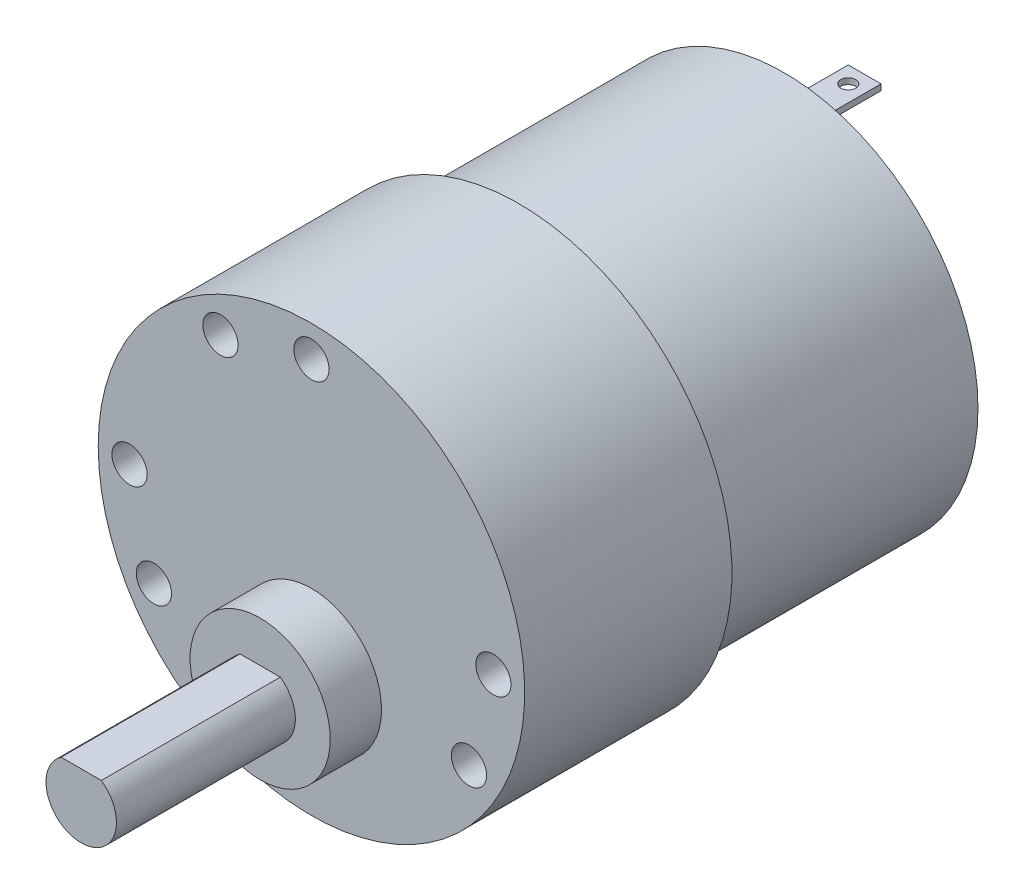
SolidWorks part; units mm, degrees
ref_plane "Front Plane" through (0, 0, 0) normal (0, 0, 1) x (1, 0, 0)
ref_plane "Top Plane" through (0, 0, 0) normal (0, 1, 0) x (1, 0, 0)
ref_plane "Right Plane" through (0, 0, 0) normal (1, 0, 0) x (0, 0, -1)
sketch "Sketch1" plane through (0, 0, 0) normal (0, 0, 1) x (1, 0, 0)
  circle A0 centre (0, 0) radius 18.161
  dimension "D1" = 36.322
extrude "Boss-Extrude1" add sketch "Sketch1" along normal blind 17.653
sketch "Sketch2" plane through (0, 0, 0) normal (0, 0, -1) x (-1, 0, 0)
  circle A0 centre (0, 0) radius 16.51
  dimension "D1" = 33.02
extrude "Boss-Extrude2" add sketch "Sketch2" along normal blind 22.606
sketch "Sketch3" plane through (0, 0, -22.606) normal (0, 0, -1) x (-1, 0, 0)
  circle A0 centre (0, 0) radius 4.5085
  dimension "D1" = 9.017
extrude "Boss-Extrude3" add sketch "Sketch3" along normal blind 3.302
sketch "Sketch4" plane through (0, 0, -22.606) normal (0, 0, -1) x (-1, 0, 0)
  circle A0 centre (0, -12.7) radius 2.413
  circle A1 centre (0, 12.7) radius 2.413
  circle A2 centre (0, 0) radius 18.161 construction
  dimension "D1" = 4.826
  dimension "D2" = 4.826
  dimension "D3" = 12.7
  dimension "D4" = 12.7
extrude "Boss-Extrude4" add sketch "Sketch4" along normal blind 1.27
sketch "Sketch5" plane through (0, 0, 17.653) normal (0, 0, 1) x (1, 0, 0)
  circle A0 centre (0, -7.366) radius 5.969
  dimension "D1" = 11.938
  dimension "D2" = 7.366
extrude "Boss-Extrude5" add sketch "Sketch5" along normal blind 4.3688
sketch "Sketch6" plane through (0, 0, 22.0218) normal (0, 0, 1) x (1, 0, 0)
  line L0 (-1.7157, -4.905) -> (1.7157, -4.905)
  arc A0 (-1.7157, -4.905) -> (1.7157, -4.905) centre (0, -7.366) ccw
  dimension "D1" = 6
  dimension "D2" = 2.461
extrude "Boss-Extrude6" add sketch "Sketch6" along normal blind 15.24
ref_axis "Axis2" through (0, 12.7, -23.876) along (0, 0, 1)
ref_axis "Axis3" through (0, -12.7, -23.876) along (0, 0, 1)
ref_plane "Plane1" through (0, 0, 0) normal (1, 0, 0) x (0, 0, -1)
ref_plane "Plane2" through (0, 12.7, 0) normal (0, 1, 0) x (0, 0, 1)
ref_plane "Plane3" through (0, -12.7, 0) normal (0, 1, 0) x (0, 0, 1)
sketch "Sketch8" plane through (0, 12.7, 0) normal (0, 1, 0) x (0, 0, 1)
  line L0 (-23.876, 2.413) -> (-23.876, -2.413) construction
  line L1 (-23.876, 1.397) -> (-29.464, 1.397)
  line L2 (-23.876, 1.397) -> (-23.876, -1.397)
  line L3 (-23.876, -1.397) -> (-29.464, -1.397)
  line L4 (-29.464, 1.397) -> (-29.464, -1.397)
  line L5 (0.6985, 0) -> (-0.6985, 0) construction
  circle A0 centre (-28.067, 0) radius 0.635
  dimension "D4" = 1.27
  dimension "D1" = 2.794
  dimension "D2" = 1.397
  dimension "D3" = 5.588
  dimension "D5" = 1.397
extrude "Boss-Extrude7" add sketch "Sketch8" along normal mid plane 0.508
pattern_circular "CirPattern1" count 2 over 360 about axis through (0, 0, -25.908) along (0, 0, 1) of "Boss-Extrude7"
sketch "Sketch9" plane through (0, 0, 17.653) normal (0, 0, 1) x (1, 0, 0)
  line L0 (0, 0) -> (0, 15.494) construction
  circle A0 centre (0, 0) radius 15.494 construction
  dimension "D1" = 30.988
hole_wizard "Ø3.0mm Dowel Hole1" positions "Sketch11" profile "Sketch12" hole size "Ø3.0" standard "ANSI Metric"
sketch "Sketch11" plane through (0, 0, 17.653) normal (0, 0, 1) x (1, 0, 0)
  point P0 (0, 15.494)
sketch "Sketch12" plane through (0, 15.494, 17.653) normal (1, 0, 0) x (0, -1, 0)
  line L0 (0, 0) -> (0, 11.0613)
  line L1 (0, 11.0613) -> (1.5, 10.16)
  line L2 (1.5, 10.16) -> (1.5, 0)
  line L5 (1.5, 0) -> (0, 0)
  line L10 (0, 11.0613) -> (-1.5, 10.16) construction
  line L11 (0, -6.35) -> (0, 107.95) construction
  dimension "Hole Dia." = 3
  dimension "Hole Depth" = 10.16
  dimension "Drill Angle" = 118
pattern_circular "CirPattern2" count 12 over 360 about axis through (0, 0, 17.653) along (0, 0, -1) skipping 1, 2, 5, 6, 10 of "Ø3.0mm Dowel Hole1"
